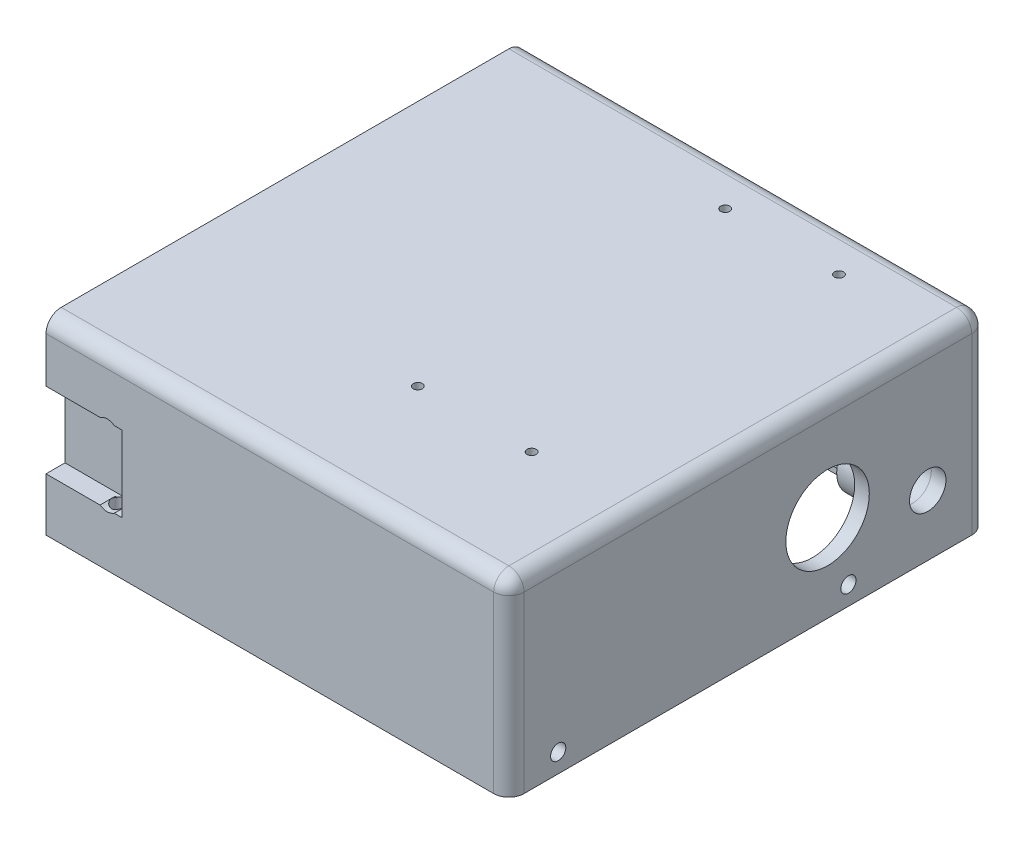
SolidWorks part; units mm, degrees
note: The reader was unsure of these and kept them because the rebuilt part matched: shared geometry of "Sketch1<4>".
ref_plane "Front Plane" through (0, 0, 0) normal (0, 0, 1) x (1, 0, 0)
ref_plane "Top Plane" through (0, 0, 0) normal (0, 1, 0) x (1, 0, 0)
ref_plane "Right Plane" through (0, 0, 0) normal (1, 0, 0) x (0, 0, -1)
sketch "Sketch1" plane through (0, 0, 0) normal (0, 1, 0) x (1, 0, 0)
  line L1 (0, 0) -> (63, 0)
  line L2 (0, 0) -> (0, 63)
  line L3 (0, 63) -> (63, 63)
  line L4 (63, 0) -> (63, 63)
  line L5 (2, 4) -> (61, 4)
  line L6 (2, 4) -> (2, 59)
  line L7 (2, 59) -> (61, 59)
  line L8 (61, 4) -> (61, 59)
  line L9 (0, 0) -> (2, 0)
  line L10 (0, 0) -> (0, 63)
  line L11 (0, 63) -> (2, 63)
  line L12 (2, 0) -> (2, 63)
  dimension "D1" = 63
  dimension "Length" = 63
  dimension "D2" = 2
  dimension "D3" = 4
  dimension "D4" = 2
  dimension "D5" = 4
extrude "Boss-Extrude2" add sketch "Sketch1" along normal blind 25 contours L1 L4 L3 L2
extrude "Cut-Extrude1" cut sketch "Sketch1<4>" along normal blind 23 contours L5 L8 L7 L6
sketch "Sketch1<4>" plane through (0, 0, 0) normal (0, 1, 0) x (1, 0, 0) same geometry as "Sketch1"
sketch "Sketch3" plane through (63, 0, 0) normal (1, 0, 0) x (0, 0, -1)
  line L0 (46.5, 10) -> (16.5, 10) construction
  line L1 (46.5, 7.5) -> (16.5, 7.5)
  line L2 (46.5, 12.5) -> (16.5, 12.5)
  line L3 (4, 0) -> (59, 0) construction
  line L4 (0, 25) -> (0, 0) construction
  arc A0 (46.5, 7.5) -> (46.5, 12.5) centre (46.5, 10) ccw
  arc A1 (16.5, 12.5) -> (16.5, 7.5) centre (16.5, 10) ccw
  point P2 (31.5, 10)
  dimension "D1" = 30
  dimension "D2" = 5
  dimension "D3" = 10
  dimension "D4" = 31.5
sketch "Sketch4" plane through (0, 23, 0) normal (0, -1, 0) x (1, 0, 0)
  line L0 (2, -4) -> (61, -4) construction
  line L1 (29.5, -4) -> (31.5, -4)
  line L2 (29.5, -4) -> (29.5, -59)
  line L3 (29.5, -59) -> (31.5, -59)
  line L4 (31.5, -4) -> (31.5, -59)
  line L5 (2, -59) -> (61, -59) construction
  line L6 (2, -4) -> (2, -59) construction
  dimension "D1" = 2
  dimension "D2" = 27.5
extrude "Boss-Extrude3" add sketch "Sketch4" along normal blind 10
fillet "Fillet1" radius 2 8 edges at (31.5, 25, -63) (0, 12.5, -63) (0, 25, -31.5) (0, 12.5, 0) (31.5, 25, 0) (63, 12.5, 0) (63, 25, -31.5) (63, 12.5, -63)
sketch "Sketch5" plane through (0, 0, 0) normal (0, -1, 0) x (-1, 0, 0)
  line L1 (0, 0) -> (-2, 0)
  line L2 (0, 0) -> (0, 63)
  line L3 (0, 63) -> (-2, 63)
  line L4 (-2, 0) -> (-2, 63)
extrude "Cut-Extrude3" cut sketch "Sketch5" against normal through all
sketch "Sketch6" plane through (2, 0, 0) normal (-1, 0, 0) x (0, 0, 1)
  line L0 (-4, 23) -> (-4, 0) construction
  line L1 (-4, 0.75) -> (-1.8, 0.75)
  line L2 (-4, 0.75) -> (-4, 2.95)
  line L3 (-4, 2.95) -> (-1.8, 2.95)
  line L4 (-1.8, 0.75) -> (-1.8, 2.95)
  line L5 (-59, 23) -> (-59, 0) construction
  line L6 (-59, 0.75) -> (-61.2, 0.75)
  line L7 (-59, 0.75) -> (-59, 2.95)
  line L8 (-59, 2.95) -> (-61.2, 2.95)
  line L9 (-61.2, 0.75) -> (-61.2, 2.95)
  line L10 (0, 0) -> (-63, 0) construction
  line L11 (0, 23) -> (0, 0) construction
  point P12 (-60.1, 2.95)
  point P17 (-1.8, 1.85)
  dimension "D1" = 2.2
  dimension "D2" = 2.2
  dimension "D3" = 2.2
  dimension "D4" = 0.75
  dimension "D5" = 0.75
  dimension "1.5" = 2.2
  dimension "D6" = 1.8
extrude "Cut-Extrude4" cut sketch "Sketch6" against normal blind 59 contours L6 L9 L8 L7 | L1 L4 L3 L2
sketch "Sketch7" plane through (0, 0, -63) normal (0, 0, -1) x (-1, 0, 0)
  line L0 (-2, 0) -> (-2, 23) construction
  line L1 (-2, 7) -> (-12, 7)
  line L2 (-2, 7) -> (-2, 17)
  line L3 (-2, 17) -> (-12, 17)
  line L4 (-12, 7) -> (-12, 17)
  line L5 (-61, 25) -> (-2, 25) construction
  dimension "D1" = 10
  dimension "D2" = 8
  dimension "D3" = 10
extrude "Cut-Extrude5" cut sketch "Sketch7" against normal blind 2.5
sketch "Sketch8" plane through (0, 7, 0) normal (0, 1, 0) x (1, 0, 0)
  line L0 (12, 60.5) -> (12, 63) construction
  line L1 (12, 60.5) -> (2, 60.5) construction
  circle A0 centre (10, 61.5) radius 0.875
  dimension "D1" = 1.75
  dimension "D2" = 2
  dimension "D3" = 1
extrude "Cut-Extrude6" cut sketch "Sketch8" against normal blind 1.5 and the other way blind 11.5
sketch "Sketch9" plane through (0, 0, 0) normal (0, 0, 1) x (1, 0, 0)
  line L0 (2, 23) -> (2, 0) construction
  line L1 (2, 7) -> (12, 7)
  line L2 (2, 7) -> (2, 17)
  line L3 (2, 17) -> (12, 17)
  line L4 (12, 7) -> (12, 17)
  line L5 (2, 25) -> (61, 25) construction
  dimension "D1" = 10
  dimension "D2" = 10
  dimension "D3" = 8
extrude "Cut-Extrude7" cut sketch "Sketch9" against normal blind 2.5
sketch "Sketch10" plane through (0, 7, 0) normal (0, 1, 0) x (1, 0, 0)
  line L0 (12, 2.5) -> (12, 0) construction
  line L1 (2, 2.5) -> (12, 2.5) construction
  circle A0 centre (10, 1.5) radius 0.875
  dimension "D1" = 1.75
  dimension "D2" = 2
  dimension "D3" = 1
extrude "Cut-Extrude8" cut sketch "Sketch10" against normal blind 1.5 and the other way blind 11.5
sketch "Sketch11" plane through (0, 0, -63) normal (0, 0, -1) x (-1, 0, 0)
  line L0 (-12, 7) -> (-2, 7) construction
  line L1 (-9.123, 7) -> (-10.8, 7)
  line L2 (-12, 12) -> (-17.0656, 12) construction
  line L3 (-12, 17) -> (-12, 7) construction
  line L4 (-9.123, 17) -> (-10.8, 17)
  spline S0 degree 2 poles (-10.8, 7) (-9.9802, 6.3956) (-9.123, 7) knots 0 0 0 1 1 1
  spline S1 degree 2 poles (-10.8, 17) (-9.9802, 17.6044) (-9.123, 17) knots 0 0 0 1 1 1
  dimension "D1" = 0.3
  dimension "D2" = 1.2
extrude "Cut-Extrude9" cut sketch "Sketch11" against normal blind 2 contours S0 L1 | S1 L4
sketch "Sketch12" plane through (0, 0, 0) normal (0, 0, 1) x (1, 0, 0)
  line L0 (2, 7) -> (12, 7) construction
  line L2 (11, 7) -> (9.1201, 7)
  line L3 (12, 12) -> (18.6065, 12) construction
  line L4 (12, 7) -> (12, 17) construction
  line L5 (11, 17) -> (9.1201, 17)
  spline S0 degree 2 poles (11, 7) (10.0566, 6.3998) (9.1201, 7) knots 0 0 0 1 1 1
  spline S1 degree 2 poles (11, 17) (10.0566, 17.6002) (9.1201, 17) knots 0 0 0 1 1 1
  dimension "D1" = 0.3
  dimension "D2" = 1
extrude "Cut-Extrude10" cut sketch "Sketch12" against normal blind 2 contours S0 L2 | S1 L5
sketch "Sketch13" plane through (0, 23, 0) normal (0, -1, 0) x (-1, 0, 0)
  line L0 (-31.5, 59) -> (-61, 59) construction
  line L1 (-49.5, 57) -> (-34.5, 57)
  line L2 (-49.5, 57) -> (-49.5, 16.5)
  line L3 (-49.5, 16.5) -> (-34.5, 16.5)
  line L4 (-34.5, 57) -> (-34.5, 16.5)
  line L6 (-42, 57) -> (-42, 16.5) construction
  line L7 (-61, 4) -> (-61, 59) construction
  circle A4 centre (-34.5, 57) radius 0.6
  circle A5 centre (-49.5, 57) radius 0.6
  circle A6 centre (-49.5, 16.5) radius 0.6
  circle A7 centre (-34.5, 16.5) radius 0.6
  dimension "D13" = 1.2
  dimension "D14" = 1.2
  dimension "D15" = 1.2
  dimension "D8" = 15
  dimension "D9" = 40.5
  dimension "D10" = 2
  dimension "D12" = 19
fillet "Fillet2" radius 0.3 12 edges at (31.5, 2.95, -4) (31.5, 2.95, -1.8) (2, 1.85, -1.8) (2, 2.95, -2.9) (31.5, 2.95, -59) (31.5, 0.75, -61.2) (31.5, 2.95, -61.2) (2, 2.95, -60.1) (2, 0.75, -60.1) (2, 1.85, -61.2) (2, 0.75, -2.9) (31.5, 0.75, -1.8)
sketch "Sketch14" plane through (0, 0, -63) normal (0, 0, -1) x (-1, 0, 0)
  line L0 (-39, 17.95) -> (-45, 17.95) construction
  line L1 (-39, 14.7) -> (-45, 14.7)
  line L2 (-39, 21.2) -> (-45, 21.2)
  line L5 (-61, 23) -> (-61, 0) construction
  line L8 (-2, 23) -> (-61, 23) construction
  arc A0 (-39, 14.7) -> (-39, 21.2) centre (-39, 17.95) ccw
  arc A1 (-45, 21.2) -> (-45, 14.7) centre (-45, 17.95) ccw
  point P2 (-42, 17.95)
  dimension "D1" = 6.5
  dimension "D2" = 1.8
  dimension "D3" = 6
  dimension "D4" = 19
extrude "Cut-Extrude12" cut sketch "Sketch14" against normal up to next contours L1 A1 L2 A0
sketch "Sketch15" plane through (29.5, 0, 0) normal (-1, 0, 0) x (0, 0, 1)
  line L0 (-4, 23) -> (-59, 23) construction
  line L1 (-4, 13) -> (-9, 13)
  line L2 (-4, 13) -> (-4, 23)
  line L3 (-4, 23) -> (-9, 23)
  line L4 (-9, 13) -> (-9, 23)
  dimension "D1" = 5
extrude "Cut-Extrude13" cut sketch "Sketch15" against normal up to next
fillet "Fillet3" radius 1 5 edges at (31.5, 18, -59) (29.5, 18, -59) (31.5, 13, -34) (29.5, 13, -34) (30.5, 13, -9)
sketch "Sketch18" plane through (63, 0, 0) normal (1, 0, 0) x (0, 0, -1)
  line L0 (61, 23) -> (2, 23) construction
  line L3 (61, 0) -> (61, 23) construction
  line L5 (4, 0) -> (59, 0) construction
  line L7 (4, 23) -> (4, 3.25) construction
  circle A2 centre (55.2, 8) radius 2.4
  circle A3 centre (42, 11.5) radius 5.5
  circle A4 centre (44.75, 2.5) radius 1
  circle A5 centre (6.5, 2.5) radius 1
  dimension "D5" = 4.8
  dimension "D1" = 11
  dimension "D4" = 2
  dimension "D9" = 2
  dimension "D2" = 11.5
  dimension "D3" = 20.5
  dimension "D6" = 8
  dimension "D7" = 5.8
  dimension "D8" = 20.5
  dimension "D10" = 38
  dimension "D11" = 40.75
  dimension "D12" = 2.5
extrude "Cut-Extrude16" cut sketch "Sketch18" against normal blind 10 draft 2 draft outward yes
sketch "Sketch19" plane through (61, 0, 0) normal (-1, 0, 0) x (0, 0, 1)
  circle A0 centre (-55.2, 8) radius 4
  circle M2 centre (-55.2, 8) radius 2.4698
  line M14 (-59, 23) -> (-59, 3.25)
  dimension "D1" = 8
extrude "Boss-Extrude4" add sketch "Sketch19" along normal blind 6 contours A0 M14 M2
extrude "Cut-Extrude17" cut sketch "Sketch13" against normal blind 6 contours A4 | A5 | A6 | A7
